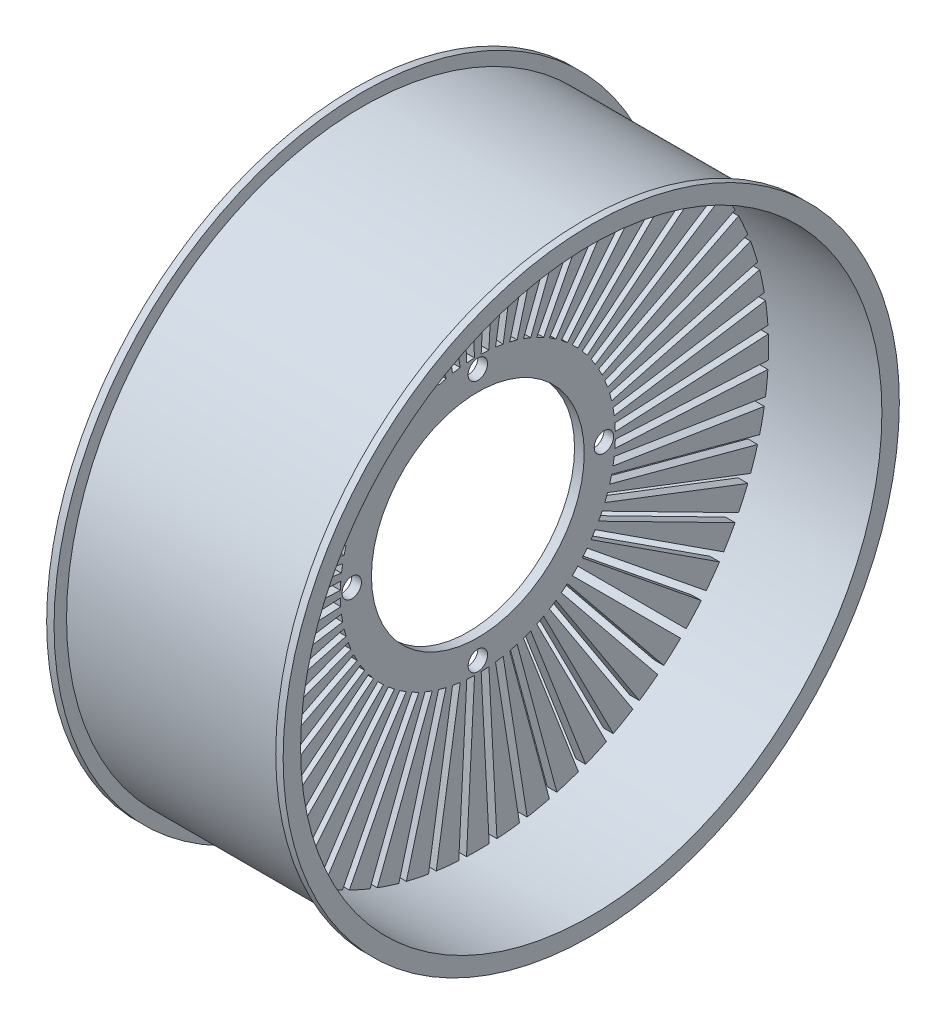
SolidWorks part; units mm, degrees
material "Stainless Steel (ferritic)"
ref_plane "Front Plane" through (0, 0, 0) normal (0, 0, 1) x (1, 0, 0)
ref_plane "Top Plane" through (0, 0, 0) normal (0, 1, 0) x (1, 0, 0)
ref_plane "Right Plane" through (0, 0, 0) normal (1, 0, 0) x (0, 0, -1)
sketch "Sketch1" plane through (0, 0, 0) normal (0, 1, 0) x (1, 0, 0)
  line L0 (0, 0) -> (0, 152.4) construction
  line L1 (-57.15, 152.4) -> (57.15, 152.4)
  line L2 (57.15, 152.4) -> (57.15, 158.8516)
  line L3 (57.15, 158.8516) -> (60.96, 158.8516)
  line L4 (60.96, 158.8516) -> (60.96, 149.86)
  line L6 (-60.96, 158.8516) -> (-60.96, 149.86)
  line L7 (-57.15, 158.8516) -> (-60.96, 158.8516)
  line L8 (-57.15, 152.4) -> (-57.15, 158.8516)
  line L11 (-145.4046, 0) -> (145.4046, 0) construction
  line L16 (-60.96, 149.86) -> (-2.5, 149.86)
  line L18 (2.5, 149.86) -> (2.5, 54.86)
  line L19 (2.5, 54.86) -> (-2.5, 54.86)
  line L20 (-2.5, 54.86) -> (-2.5, 149.86)
  line L21 (2.5, 149.86) -> (60.96, 149.86)
  point P6 (0, 152.4)
  point P11 (0, 149.86)
  point P13 (57.15, 155.6258)
  point P17 (0, 0)
  point P20 (-1.25, 149.86)
  point P26 (0, 0)
  dimension "D1" = 3.81
  dimension "D2" = 114.3
  dimension "D4" = 6.4516
revolve "Revolve2" add sketch "Sketch1" angle 360 about L11
ref_axis "Axis1" through (302.1146, 0, 0) along (-1, 0, 0)
sketch "Sketch2" plane through (-2.5, 0, 0) normal (-1, 0, 0) x (0, 0, 1)
  circle A0 centre (0, 0) radius 65 construction
  circle A1 centre (-65, 0) radius 5
  circle A2 centre (0, 65) radius 5
  circle A3 centre (65, 0) radius 5
  circle A4 centre (0, -65) radius 5
extrude "Cut-Extrude1" cut sketch "Sketch2" against normal blind 10
sketch "Sketch3" plane through (-2.5, 0, 0) normal (-1, 0, 0) x (0, 0, 1)
  line L3 (-48.6987, -51.5271) -> (-104.5434, -107.3718)
  line L7 (-48.6987, -51.5271) -> (-51.5271, -48.6987)
  line L9 (-51.5271, -48.6987) -> (-107.3718, -104.5434)
  line L115 (-53.818, -46.1544) -> (-56.3352, -43.0459)
  line L116 (-56.3352, -43.0459) -> (-117.7114, -92.7473)
  line L117 (-53.818, -46.1544) -> (-115.1941, -95.8558)
  line L118 (-58.3476, -40.2761) -> (-60.5262, -36.9214)
  line L119 (-60.5262, -36.9214) -> (-126.7613, -79.935)
  line L120 (-58.3476, -40.2761) -> (-124.5827, -83.2897)
  line L121 (-62.238, -33.9565) -> (-64.0539, -30.3925)
  line L122 (-64.0539, -30.3925) -> (-134.4223, -66.2469)
  line L123 (-62.238, -33.9565) -> (-132.6064, -69.811)
  line L124 (-65.4464, -27.2648) -> (-66.8799, -23.5305)
  line L125 (-66.8799, -23.5305) -> (-140.6106, -51.8331)
  line L126 (-65.4464, -27.2648) -> (-139.1772, -55.5674)
  line L127 (-67.9379, -20.2744) -> (-68.9731, -16.4107)
  line L128 (-68.9731, -16.4107) -> (-145.2584, -36.8513)
  line L129 (-67.9379, -20.2744) -> (-144.2231, -40.715)
  line L130 (-69.6849, -13.0619) -> (-70.3107, -9.1112)
  line L131 (-70.3107, -9.1112) -> (-148.3147, -21.4658)
  line L132 (-69.6849, -13.0619) -> (-147.6889, -25.4166)
  line L133 (-70.6686, -5.7063) -> (-70.8779, -1.7118)
  line L134 (-70.8779, -1.7118) -> (-149.746, -5.8451)
  line L135 (-70.6686, -5.7063) -> (-149.5366, -9.8396)
  line L136 (-70.8779, 1.7118) -> (-70.6686, 5.7063)
  line L137 (-70.6686, 5.7063) -> (-149.5366, 9.8396)
  line L138 (-70.8779, 1.7118) -> (-149.746, 5.8451)
  line L139 (-70.3107, 9.1112) -> (-69.6849, 13.0619)
  line L140 (-69.6849, 13.0619) -> (-147.6889, 25.4166)
  line L141 (-70.3107, 9.1112) -> (-148.3147, 21.4658)
  line L142 (-68.9731, 16.4107) -> (-67.9379, 20.2744)
  line L143 (-67.9379, 20.2744) -> (-144.2231, 40.715)
  line L144 (-68.9731, 16.4107) -> (-145.2584, 36.8513)
  line L145 (-66.8799, 23.5305) -> (-65.4464, 27.2648)
  line L146 (-65.4464, 27.2648) -> (-139.1772, 55.5674)
  line L147 (-66.8799, 23.5305) -> (-140.6106, 51.8331)
  line L148 (-64.0539, 30.3925) -> (-62.238, 33.9565)
  line L149 (-62.238, 33.9565) -> (-132.6064, 69.811)
  line L150 (-64.0539, 30.3925) -> (-134.4223, 66.2469)
  line L151 (-60.5262, 36.9214) -> (-58.3476, 40.2761)
  line L152 (-58.3476, 40.2761) -> (-124.5827, 83.2897)
  line L153 (-60.5262, 36.9214) -> (-126.7613, 79.935)
  line L154 (-56.3352, 43.0459) -> (-53.818, 46.1544)
  line L155 (-53.818, 46.1544) -> (-115.1941, 95.8558)
  line L156 (-56.3352, 43.0459) -> (-117.7114, 92.7473)
  line L157 (-51.5271, 48.6987) -> (-48.6987, 51.5271)
  line L158 (-48.6987, 51.5271) -> (-104.5434, 107.3718)
  line L159 (-51.5271, 48.6987) -> (-107.3718, 104.5434)
  line L160 (-46.1544, 53.818) -> (-43.0459, 56.3352)
  line L161 (-43.0459, 56.3352) -> (-92.7473, 117.7114)
  line L162 (-46.1544, 53.818) -> (-95.8558, 115.1941)
  line L163 (-40.2761, 58.3476) -> (-36.9214, 60.5262)
  line L164 (-36.9214, 60.5262) -> (-79.935, 126.7613)
  line L165 (-40.2761, 58.3476) -> (-83.2897, 124.5827)
  line L166 (-33.9565, 62.238) -> (-30.3925, 64.0539)
  line L167 (-30.3925, 64.0539) -> (-66.2469, 134.4223)
  line L168 (-33.9565, 62.238) -> (-69.811, 132.6064)
  line L169 (-27.2648, 65.4464) -> (-23.5305, 66.8799)
  line L170 (-23.5305, 66.8799) -> (-51.8331, 140.6106)
  line L171 (-27.2648, 65.4464) -> (-55.5674, 139.1772)
  line L172 (-20.2744, 67.9379) -> (-16.4107, 68.9731)
  line L173 (-16.4107, 68.9731) -> (-36.8513, 145.2584)
  line L174 (-20.2744, 67.9379) -> (-40.715, 144.2231)
  line L175 (-13.0619, 69.6849) -> (-9.1112, 70.3107)
  line L176 (-9.1112, 70.3107) -> (-21.4658, 148.3147)
  line L177 (-13.0619, 69.6849) -> (-25.4166, 147.6889)
  line L178 (-5.7063, 70.6686) -> (-1.7118, 70.8779)
  line L179 (-1.7118, 70.8779) -> (-5.8451, 149.746)
  line L180 (-5.7063, 70.6686) -> (-9.8396, 149.5366)
  line L181 (1.7118, 70.8779) -> (5.7063, 70.6686)
  line L182 (5.7063, 70.6686) -> (9.8396, 149.5366)
  line L183 (1.7118, 70.8779) -> (5.8451, 149.746)
  line L184 (9.1112, 70.3107) -> (13.0619, 69.6849)
  line L185 (13.0619, 69.6849) -> (25.4166, 147.6889)
  line L186 (9.1112, 70.3107) -> (21.4658, 148.3147)
  line L187 (16.4107, 68.9731) -> (20.2744, 67.9379)
  line L188 (20.2744, 67.9379) -> (40.715, 144.2231)
  line L189 (16.4107, 68.9731) -> (36.8513, 145.2584)
  line L190 (23.5305, 66.8799) -> (27.2648, 65.4464)
  line L191 (27.2648, 65.4464) -> (55.5674, 139.1772)
  line L192 (23.5305, 66.8799) -> (51.8331, 140.6106)
  line L193 (30.3925, 64.0539) -> (33.9565, 62.238)
  line L194 (33.9565, 62.238) -> (69.811, 132.6064)
  line L195 (30.3925, 64.0539) -> (66.2469, 134.4223)
  line L196 (36.9214, 60.5262) -> (40.2761, 58.3476)
  line L197 (40.2761, 58.3476) -> (83.2897, 124.5827)
  line L198 (36.9214, 60.5262) -> (79.935, 126.7613)
  line L199 (43.0459, 56.3352) -> (46.1544, 53.818)
  line L200 (46.1544, 53.818) -> (95.8558, 115.1941)
  line L201 (43.0459, 56.3352) -> (92.7473, 117.7114)
  line L202 (48.6987, 51.5271) -> (51.5271, 48.6987)
  line L203 (51.5271, 48.6987) -> (107.3718, 104.5434)
  line L204 (48.6987, 51.5271) -> (104.5434, 107.3718)
  line L205 (53.818, 46.1544) -> (56.3352, 43.0459)
  line L206 (56.3352, 43.0459) -> (117.7114, 92.7473)
  line L207 (53.818, 46.1544) -> (115.1941, 95.8558)
  line L208 (58.3476, 40.2761) -> (60.5262, 36.9214)
  line L209 (60.5262, 36.9214) -> (126.7613, 79.935)
  line L210 (58.3476, 40.2761) -> (124.5827, 83.2897)
  line L211 (62.238, 33.9565) -> (64.0539, 30.3925)
  line L212 (64.0539, 30.3925) -> (134.4223, 66.2469)
  line L213 (62.238, 33.9565) -> (132.6064, 69.811)
  line L214 (65.4464, 27.2648) -> (66.8799, 23.5305)
  line L215 (66.8799, 23.5305) -> (140.6106, 51.8331)
  line L216 (65.4464, 27.2648) -> (139.1772, 55.5674)
  line L217 (67.9379, 20.2744) -> (68.9731, 16.4107)
  line L218 (68.9731, 16.4107) -> (145.2584, 36.8513)
  line L219 (67.9379, 20.2744) -> (144.2231, 40.715)
  line L220 (69.6849, 13.0619) -> (70.3107, 9.1112)
  line L221 (70.3107, 9.1112) -> (148.3147, 21.4658)
  line L222 (69.6849, 13.0619) -> (147.6889, 25.4166)
  line L223 (70.6686, 5.7063) -> (70.8779, 1.7118)
  line L224 (70.8779, 1.7118) -> (149.746, 5.8451)
  line L225 (70.6686, 5.7063) -> (149.5366, 9.8396)
  line L226 (70.8779, -1.7118) -> (70.6686, -5.7063)
  line L227 (70.6686, -5.7063) -> (149.5366, -9.8396)
  line L228 (70.8779, -1.7118) -> (149.746, -5.8451)
  line L229 (70.3107, -9.1112) -> (69.6849, -13.0619)
  line L230 (69.6849, -13.0619) -> (147.6889, -25.4166)
  line L231 (70.3107, -9.1112) -> (148.3147, -21.4658)
  line L232 (68.9731, -16.4107) -> (67.9379, -20.2744)
  line L233 (67.9379, -20.2744) -> (144.2231, -40.715)
  line L234 (68.9731, -16.4107) -> (145.2584, -36.8513)
  line L235 (66.8799, -23.5305) -> (65.4464, -27.2648)
  line L236 (65.4464, -27.2648) -> (139.1772, -55.5674)
  line L237 (66.8799, -23.5305) -> (140.6106, -51.8331)
  line L238 (64.0539, -30.3925) -> (62.238, -33.9565)
  line L239 (62.238, -33.9565) -> (132.6064, -69.811)
  line L240 (64.0539, -30.3925) -> (134.4223, -66.2469)
  line L241 (60.5262, -36.9214) -> (58.3476, -40.2761)
  line L242 (58.3476, -40.2761) -> (124.5827, -83.2897)
  line L243 (60.5262, -36.9214) -> (126.7613, -79.935)
  line L244 (56.3352, -43.0459) -> (53.818, -46.1544)
  line L245 (53.818, -46.1544) -> (115.1941, -95.8558)
  line L246 (56.3352, -43.0459) -> (117.7114, -92.7473)
  line L247 (51.5271, -48.6987) -> (48.6987, -51.5271)
  line L248 (48.6987, -51.5271) -> (104.5434, -107.3718)
  line L249 (51.5271, -48.6987) -> (107.3718, -104.5434)
  line L250 (46.1544, -53.818) -> (43.0459, -56.3352)
  line L251 (43.0459, -56.3352) -> (92.7473, -117.7114)
  line L252 (46.1544, -53.818) -> (95.8558, -115.1941)
  line L253 (40.2761, -58.3476) -> (36.9214, -60.5262)
  line L254 (36.9214, -60.5262) -> (79.935, -126.7613)
  line L255 (40.2761, -58.3476) -> (83.2897, -124.5827)
  line L256 (33.9565, -62.238) -> (30.3925, -64.0539)
  line L257 (30.3925, -64.0539) -> (66.2469, -134.4223)
  line L258 (33.9565, -62.238) -> (69.811, -132.6064)
  line L259 (27.2648, -65.4464) -> (23.5305, -66.8799)
  line L260 (23.5305, -66.8799) -> (51.8331, -140.6106)
  line L261 (27.2648, -65.4464) -> (55.5674, -139.1772)
  line L262 (20.2744, -67.9379) -> (16.4107, -68.9731)
  line L263 (16.4107, -68.9731) -> (36.8513, -145.2584)
  line L264 (20.2744, -67.9379) -> (40.715, -144.2231)
  line L265 (13.0619, -69.6849) -> (9.1112, -70.3107)
  line L266 (9.1112, -70.3107) -> (21.4658, -148.3147)
  line L267 (13.0619, -69.6849) -> (25.4166, -147.6889)
  line L268 (5.7063, -70.6686) -> (1.7118, -70.8779)
  line L269 (1.7118, -70.8779) -> (5.8451, -149.746)
  line L270 (5.7063, -70.6686) -> (9.8396, -149.5366)
  line L271 (-1.7118, -70.8779) -> (-5.7063, -70.6686)
  line L272 (-5.7063, -70.6686) -> (-9.8396, -149.5366)
  line L273 (-1.7118, -70.8779) -> (-5.8451, -149.746)
  line L274 (-9.1112, -70.3107) -> (-13.0619, -69.6849)
  line L275 (-13.0619, -69.6849) -> (-25.4166, -147.6889)
  line L276 (-9.1112, -70.3107) -> (-21.4658, -148.3147)
  line L277 (-16.4107, -68.9731) -> (-20.2744, -67.9379)
  line L278 (-20.2744, -67.9379) -> (-40.715, -144.2231)
  line L279 (-16.4107, -68.9731) -> (-36.8513, -145.2584)
  line L280 (-23.5305, -66.8799) -> (-27.2648, -65.4464)
  line L281 (-27.2648, -65.4464) -> (-55.5674, -139.1772)
  line L282 (-23.5305, -66.8799) -> (-51.8331, -140.6106)
  line L283 (-30.3925, -64.0539) -> (-33.9565, -62.238)
  line L284 (-33.9565, -62.238) -> (-69.811, -132.6064)
  line L285 (-30.3925, -64.0539) -> (-66.2469, -134.4223)
  line L286 (-36.9214, -60.5262) -> (-40.2761, -58.3476)
  line L287 (-40.2761, -58.3476) -> (-83.2897, -124.5827)
  line L288 (-36.9214, -60.5262) -> (-79.935, -126.7613)
  line L289 (-43.0459, -56.3352) -> (-46.1544, -53.818)
  line L290 (-46.1544, -53.818) -> (-95.8558, -115.1941)
  line L291 (-43.0459, -56.3352) -> (-92.7473, -117.7114)
  arc A0 (-115.1941, -95.8558) -> (-117.7114, -92.7473) centre (0, 0) cw
  circle A1 centre (0, 0) radius 149.86 construction
  arc A2 (-104.5434, -107.3718) -> (-107.3718, -104.5434) centre (0, 0) cw
  arc A38 (-124.5827, -83.2897) -> (-126.7613, -79.935) centre (0, 0) cw
  arc A39 (-132.6064, -69.811) -> (-134.4223, -66.2469) centre (0, 0) cw
  arc A40 (-139.1772, -55.5674) -> (-140.6106, -51.8331) centre (0, 0) cw
  arc A41 (-144.2231, -40.715) -> (-145.2584, -36.8513) centre (0, 0) cw
  arc A42 (-147.6889, -25.4166) -> (-148.3147, -21.4658) centre (0, 0) cw
  arc A43 (-149.5366, -9.8396) -> (-149.746, -5.8451) centre (0, 0) cw
  arc A44 (-149.746, 5.8451) -> (-149.5366, 9.8396) centre (0, 0) cw
  arc A45 (-148.3147, 21.4658) -> (-147.6889, 25.4166) centre (0, 0) cw
  arc A46 (-145.2584, 36.8513) -> (-144.2231, 40.715) centre (0, 0) cw
  arc A47 (-140.6106, 51.8331) -> (-139.1772, 55.5674) centre (0, 0) cw
  arc A48 (-134.4223, 66.2469) -> (-132.6064, 69.811) centre (0, 0) cw
  arc A49 (-126.7613, 79.935) -> (-124.5827, 83.2897) centre (0, 0) cw
  arc A50 (-117.7114, 92.7473) -> (-115.1941, 95.8558) centre (0, 0) cw
  arc A51 (-107.3718, 104.5434) -> (-104.5434, 107.3718) centre (0, 0) cw
  arc A52 (-95.8558, 115.1941) -> (-92.7473, 117.7114) centre (0, 0) cw
  arc A53 (-83.2897, 124.5827) -> (-79.935, 126.7613) centre (0, 0) cw
  arc A54 (-69.811, 132.6064) -> (-66.2469, 134.4223) centre (0, 0) cw
  arc A55 (-55.5674, 139.1772) -> (-51.8331, 140.6106) centre (0, 0) cw
  arc A56 (-40.715, 144.2231) -> (-36.8513, 145.2584) centre (0, 0) cw
  arc A57 (-25.4166, 147.6889) -> (-21.4658, 148.3147) centre (0, 0) cw
  arc A58 (-9.8396, 149.5366) -> (-5.8451, 149.746) centre (0, 0) cw
  arc A59 (5.8451, 149.746) -> (9.8396, 149.5366) centre (0, 0) cw
  arc A60 (21.4658, 148.3147) -> (25.4166, 147.6889) centre (0, 0) cw
  arc A61 (36.8513, 145.2584) -> (40.715, 144.2231) centre (0, 0) cw
  arc A62 (51.8331, 140.6106) -> (55.5674, 139.1772) centre (0, 0) cw
  arc A63 (66.2469, 134.4223) -> (69.811, 132.6064) centre (0, 0) cw
  arc A64 (79.935, 126.7613) -> (83.2897, 124.5827) centre (0, 0) cw
  arc A65 (92.7473, 117.7114) -> (95.8558, 115.1941) centre (0, 0) cw
  arc A66 (104.5434, 107.3718) -> (107.3718, 104.5434) centre (0, 0) cw
  arc A67 (115.1941, 95.8558) -> (117.7114, 92.7473) centre (0, 0) cw
  arc A68 (124.5827, 83.2897) -> (126.7613, 79.935) centre (0, 0) cw
  arc A69 (132.6064, 69.811) -> (134.4223, 66.2469) centre (0, 0) cw
  arc A70 (139.1772, 55.5674) -> (140.6106, 51.8331) centre (0, 0) cw
  arc A71 (144.2231, 40.715) -> (145.2584, 36.8513) centre (0, 0) cw
  arc A72 (147.6889, 25.4166) -> (148.3147, 21.4658) centre (0, 0) cw
  arc A73 (149.5366, 9.8396) -> (149.746, 5.8451) centre (0, 0) cw
  arc A74 (149.746, -5.8451) -> (149.5366, -9.8396) centre (0, 0) cw
  arc A75 (148.3147, -21.4658) -> (147.6889, -25.4166) centre (0, 0) cw
  arc A76 (145.2584, -36.8513) -> (144.2231, -40.715) centre (0, 0) cw
  arc A77 (140.6106, -51.8331) -> (139.1772, -55.5674) centre (0, 0) cw
  arc A78 (134.4223, -66.2469) -> (132.6064, -69.811) centre (0, 0) cw
  arc A79 (126.7613, -79.935) -> (124.5827, -83.2897) centre (0, 0) cw
  arc A80 (117.7114, -92.7473) -> (115.1941, -95.8558) centre (0, 0) cw
  arc A81 (107.3718, -104.5434) -> (104.5434, -107.3718) centre (0, 0) cw
  arc A82 (95.8558, -115.1941) -> (92.7473, -117.7114) centre (0, 0) cw
  arc A83 (83.2897, -124.5827) -> (79.935, -126.7613) centre (0, 0) cw
  arc A84 (69.811, -132.6064) -> (66.2469, -134.4223) centre (0, 0) cw
  arc A85 (55.5674, -139.1772) -> (51.8331, -140.6106) centre (0, 0) cw
  arc A86 (40.715, -144.2231) -> (36.8513, -145.2584) centre (0, 0) cw
  arc A87 (25.4166, -147.6889) -> (21.4658, -148.3147) centre (0, 0) cw
  arc A88 (9.8396, -149.5366) -> (5.8451, -149.746) centre (0, 0) cw
  arc A89 (-5.8451, -149.746) -> (-9.8396, -149.5366) centre (0, 0) cw
  arc A90 (-21.4658, -148.3147) -> (-25.4166, -147.6889) centre (0, 0) cw
  arc A91 (-36.8513, -145.2584) -> (-40.715, -144.2231) centre (0, 0) cw
  arc A92 (-51.8331, -140.6106) -> (-55.5674, -139.1772) centre (0, 0) cw
  arc A93 (-66.2469, -134.4223) -> (-69.811, -132.6064) centre (0, 0) cw
  arc A94 (-79.935, -126.7613) -> (-83.2897, -124.5827) centre (0, 0) cw
  arc A95 (-92.7473, -117.7114) -> (-95.8558, -115.1941) centre (0, 0) cw
  point P150 (0, 0)
  point P247 (0, 0)
  dimension "D1" = 60
extrude "Cut-Extrude2" cut sketch "Sketch3" against normal blind 61
